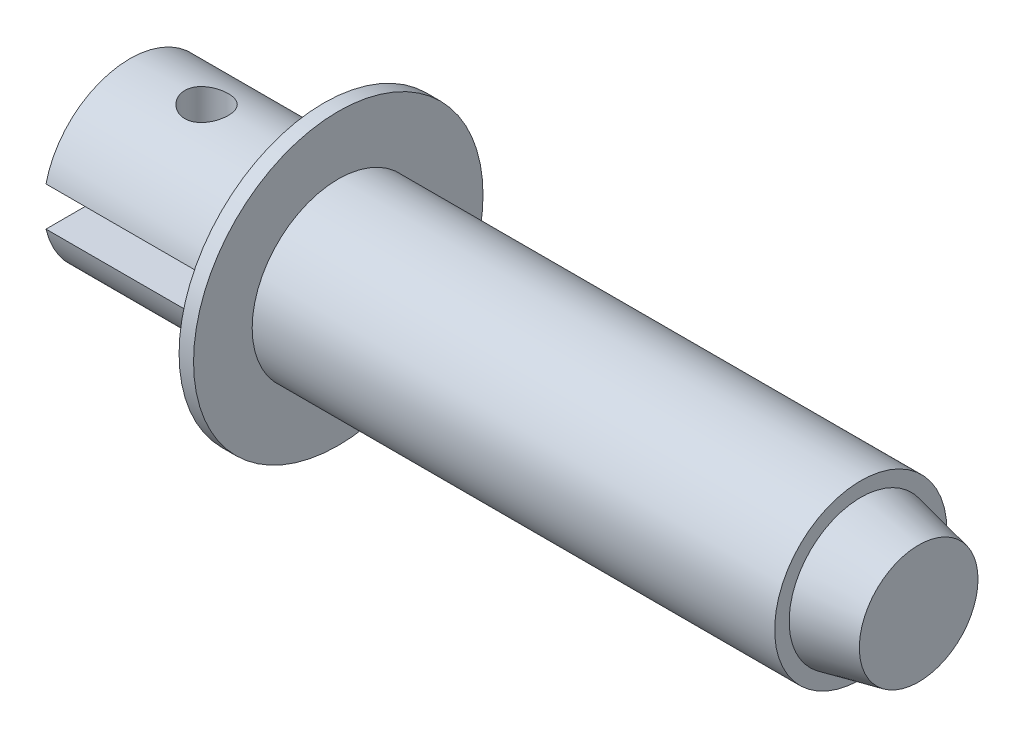
SolidWorks part; units mm, degrees
ref_plane "Alzado" through (0, 0, 0) normal (0, 0, 1) x (1, 0, 0)
ref_plane "Planta" through (0, 0, 0) normal (0, 1, 0) x (1, 0, 0)
ref_plane "Vista lateral" through (0, 0, 0) normal (1, 0, 0) x (0, 0, -1)
sketch "Croquis1" plane through (0, 0, 0) normal (0, 0, 1) x (1, 0, 0)
  line L3 (-0.4407, 5.95) -> (50.0593, 5.95)
  line L4 (50.0593, 5.95) -> (50.0593, 4.95)
  line L5 (50.0593, 4.95) -> (54.0593, 4.1)
  line L6 (54.0593, 4.1) -> (54.0593, 0)
  line L7 (54.0593, 0) -> (0, 0)
  line L8 (-0.4407, 5.95) -> (-0.4407, 0)
  line L9 (-0.4407, 0) -> (0, 0)
  point P1 (-11.9, 5.6446)
  point P3 (53.0799, 4.1)
  point P6 (0, 0)
  point P10 (-11.9, 5.631)
  point P11 (0, 0)
  point P12 (0, 0)
  dimension "D1" = 54.5
  dimension "D3" = 5.95
  dimension "D5" = 4
  dimension "D6" = 4.1
  dimension "D7" = 1
revolve "Revolución1" add sketch "Croquis1" angle 360 about L7
sketch "Croquis2" plane through (0, 0, 0) normal (0, 0, 1) x (1, 0, 0)
  line L0 (-0.4407, 5.95) -> (-0.4407, -5.95) construction
  line L1 (-0.4407, 5.95) -> (-0.4407, -5.95)
  line L2 (-0.4407, 0) -> (50.0593, 0) construction
  line L3 (-0.4407, 1.35) -> (11.4593, 1.35)
  line L4 (-0.4407, 1.35) -> (-0.4407, -1.35)
  line L5 (-0.4407, -1.35) -> (11.4593, -1.35)
  line L6 (11.4593, 1.35) -> (11.4593, -1.35)
  line L7 (50.0593, -5.95) -> (50.0593, 5.95) construction
  point P12 (-0.4407, 0)
  dimension "D1" = 2.7
  dimension "D2" = 11.9
extrude "Cortar-Extruir1" cut sketch "Croquis2" against normal blind 10 and the other way blind 10 contours L3 L6 L5 L4
sketch "Croquis3" plane through (0, 0, 0) normal (0, 1, 0) x (1, 0, 0)
  line L0 (4.8593, 0) -> (3.3593, 0) construction
  line L1 (3.3593, 0) -> (-0.4407, 0) construction
  line L2 (-0.4407, 5.7948) -> (-0.4407, -5.7948) construction
  line L3 (4.8593, 0) -> (6.3593, 0) construction
  line L4 (6.3593, 0) -> (-0.4407, 0)
  circle A0 centre (4.8593, 0) radius 1.5
  dimension "D2" = 3
  dimension "D1" = 3.8
extrude "Cortar-Extruir2" cut sketch "Croquis3" against normal blind 10 and the other way blind 10 contours L4 A0 | A0 region at (4.8593, 0, -0.6366)
sketch "Croquis4" plane through (0, 0, 0) normal (0, 1, 0) x (1, 0, 0)
  line L0 (0, 0) -> (55.174, 0) construction
  line L1 (-0.4407, 5.7948) -> (-0.4407, -5.7948) construction
  line L2 (12.9593, 0) -> (13.9593, 0)
  line L3 (12.9593, 0) -> (12.9593, 10)
  line L4 (12.9593, 10) -> (13.9593, 10)
  line L5 (13.9593, 0) -> (13.9593, 10)
  dimension "D1" = 10
  dimension "D2" = 1
  dimension "D3" = 13.4
revolve "Revolución2" add sketch "Croquis4" angle 360 about L0
